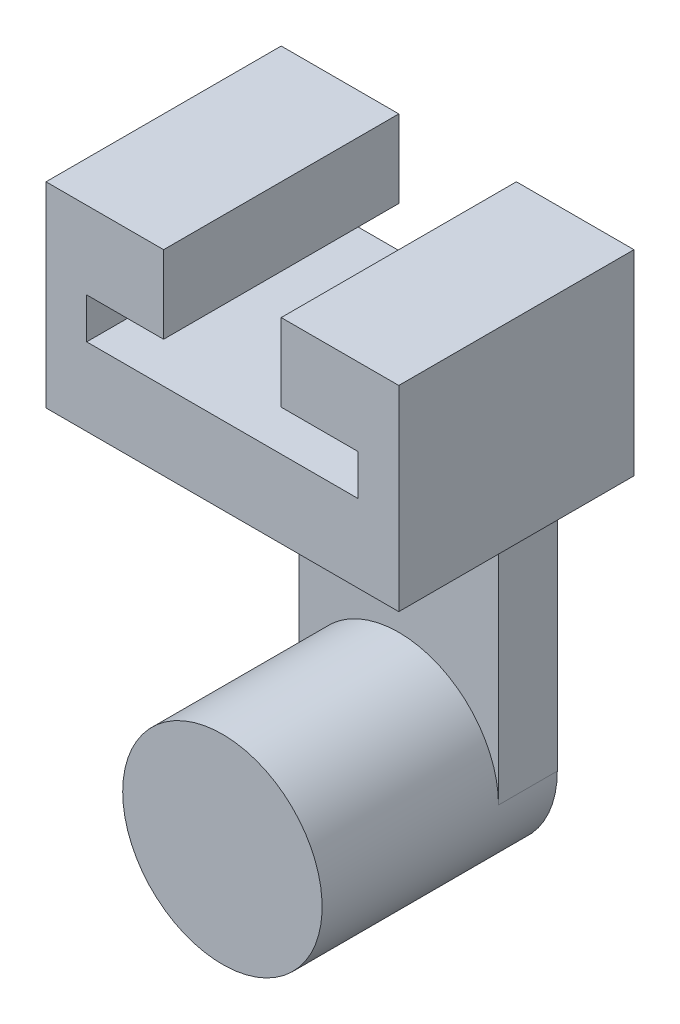
SolidWorks part; units mm, degrees
material "6061-T6 (SS)"
ref_plane "Front Plane" through (0, 0, 0) normal (0, 0, 1) x (1, 0, 0)
ref_plane "Top Plane" through (0, 0, 0) normal (0, 1, 0) x (1, 0, 0)
ref_plane "Right Plane" through (0, 0, 0) normal (1, 0, 0) x (0, 0, -1)
sketch "Sketch1" plane through (0, 0, 0) normal (0, 0, 1) x (1, 0, 0)
  line L1 (0, 0) -> (-38.1, 0)
  line L2 (0, 0) -> (0, 8.382)
  line L3 (0, 8.382) -> (-38.1, 8.382)
  line L4 (-38.1, 0) -> (-38.1, 8.382)
  dimension "D2" = 8.382
  dimension "D1" = 38.1
extrude "Boss-Extrude1" add sketch "Sketch1" along normal blind 25.4
sketch "Sketch2" plane through (0, 0, 25.4) normal (0, 0, 1) x (1, 0, 0)
  line L1 (-38.1, 8.382) -> (-33.7058, 8.382)
  line L2 (-38.1, 8.382) -> (-38.1, 12.7762)
  line L3 (-38.1, 12.7762) -> (-33.7058, 12.7762)
  line L4 (-33.7058, 8.382) -> (-33.7058, 12.7762)
  line L5 (0, 8.382) -> (-4.3942, 8.382)
  line L6 (0, 8.382) -> (0, 12.7762)
  line L7 (0, 12.7762) -> (-4.3942, 12.7762)
  line L8 (-4.3942, 8.382) -> (-4.3942, 12.7762)
  dimension "D1" = 4.3942
extrude "Boss-Extrude2" add sketch "Sketch2" against normal blind 25.4
sketch "Sketch3" plane through (0, 0, 25.4) normal (0, 0, 1) x (1, 0, 0)
  line L1 (-38.1, 12.7762) -> (-25.4, 12.7762)
  line L2 (-38.1, 12.7762) -> (-38.1, 21.1582)
  line L3 (-38.1, 21.1582) -> (-25.4, 21.1582)
  line L4 (-25.4, 12.7762) -> (-25.4, 21.1582)
  line L5 (0, 12.7762) -> (-12.7, 12.7762)
  line L6 (0, 12.7762) -> (0, 21.1582)
  line L7 (0, 21.1582) -> (-12.7, 21.1582)
  line L8 (-12.7, 12.7762) -> (-12.7, 21.1582)
  dimension "D1" = 12.7
  dimension "D2" = 8.382
extrude "Boss-Extrude3" add sketch "Sketch3" against normal blind 25.4
sketch "Sketch4" plane through (0, 0, 0) normal (0, 0, -1) x (-1, 0, 0)
  line L2 (29.8196, 0) -> (29.8196, -31.75)
  line L3 (8.2804, 0) -> (8.2804, -31.75)
  line L5 (8.2804, 0) -> (29.8196, 0)
  line L6 (8.2804, -31.75) -> (29.8196, -31.75)
  dimension "D1" = 21.5392
  dimension "D2" = 31.75
  dimension "D3" = 8.2804
  dimension "D4" = 8.2804
extrude "Boss-Extrude4" add sketch "Sketch4" against normal blind 6.35 separate body
sketch "Sketch5" plane through (0, 0, 0) normal (0, 0, -1) x (-1, 0, 0)
  line L0 (8.2804, -31.75) -> (29.8196, -31.75) construction
  line L1 (38.1, 0) -> (0, 0) construction
  circle A0 centre (19.05, -31.75) radius 10.7696
  point P6 (19.05, 0)
  dimension "D2" = 21.5392
  dimension "D1" = 31.75
extrude "Boss-Extrude5" add sketch "Sketch5" against normal blind 25.4
combine bodies "Combine1" operation type add bodies to combine 105 103
ref_axis "Axis1" through (-19.05, -31.75, 25.4) along (0, 0, -1)
equation "\"A_Diameter\"= 0.848in"
equation "\"Link_Length\"= 1.25in"
equation "\"D2@Sketch5\"=\"A_Diameter\""
equation "\"D2@Sketch4\"=\"Link_Length\""
equation "\"E_Thick\"= 0.33in'E_"
equation "\"E_width\"= 0.5in"
equation "\"D2@Sketch3\"=\"E_Thick\""
equation "\"D1@Sketch3\"=\"E_width\""
equation "\"C_Length\"= 1.50in"
equation "\"C_width\"= 0.33in"
equation "\"D1@Sketch1\"=\"C_Length\""
equation "\"D2@Sketch1\"=\"C_width\""
equation "\"C_Thick\"= 1.00in"
equation "\"D1@Boss-Extrude1\"=\"C_Thick\""
equation "\"D1@Boss-Extrude2\"=\"C_Thick\""
equation "\"D1@Boss-Extrude3\"=\"C_Thick\""
equation "\"D1@Boss-Extrude5\"=\"C_Thick\""
